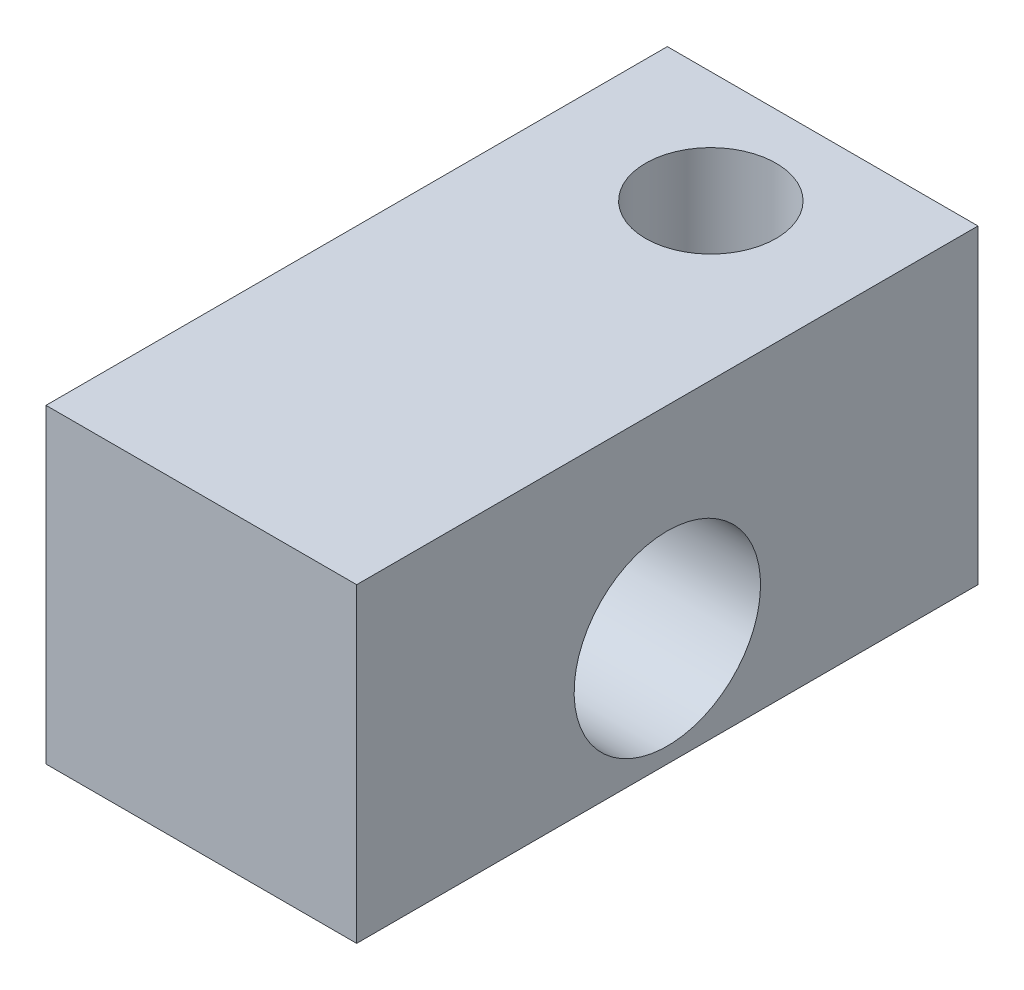
SolidWorks part; units mm, degrees
ref_plane "Front Plane" through (0, 0, 0) normal (0, 0, 1) x (1, 0, 0)
ref_plane "Top Plane" through (0, 0, 0) normal (0, 1, 0) x (1, 0, 0)
ref_plane "Right Plane" through (0, 0, 0) normal (1, 0, 0) x (0, 0, -1)
sketch "Sketch1" plane through (0, 0, 0) normal (0, 0, 1) x (1, 0, 0)
  line L1 (0, 0) -> (5, 0)
  line L2 (0, 0) -> (0, -5)
  line L3 (0, -5) -> (5, -5)
  line L4 (5, 0) -> (5, -5)
  dimension "D1" = 5
  dimension "D2" = 5
extrude "Boss-Extrude1" add sketch "Sketch1" along normal blind 10
sketch "Sketch2" plane through (5, 0, 0) normal (1, 0, 0) x (0, 0, -1)
  line L0 (-10, -5) -> (0, -5) construction
  line L1 (-5, -3.25) -> (-5, -5) construction
  circle A0 centre (-5, -3.25) radius 1.5
  dimension "D1" = 3
  dimension "D2" = 1.75
extrude "Cut-Extrude1" cut sketch "Sketch2" against normal up to next
sketch "Sketch3" plane through (0, 0, 0) normal (0, 1, 0) x (1, 0, 0)
  line L0 (2.5, -0.75) -> (2.5, 0) construction
  line L1 (5, 0) -> (0, 0) construction
  circle A0 centre (2.5, -1.8) radius 1.05
  dimension "D1" = 2.1
  dimension "D2" = 0.75
extrude "Cut-Extrude2" cut sketch "Sketch3" against normal blind 3.25
sketch "Sketch4" plane through (0, -5, 0) normal (0, -1, 0) x (1, 0, 0)
  line L0 (2.5, 9.25) -> (2.5, 10) construction
  line L1 (0, 10) -> (5, 10) construction
  circle A0 centre (2.5, 8.2) radius 1.05
  dimension "D2" = 2.1
  dimension "D1" = 0.75
extrude "Cut-Extrude3" cut sketch "Sketch4" against normal blind 1.75
